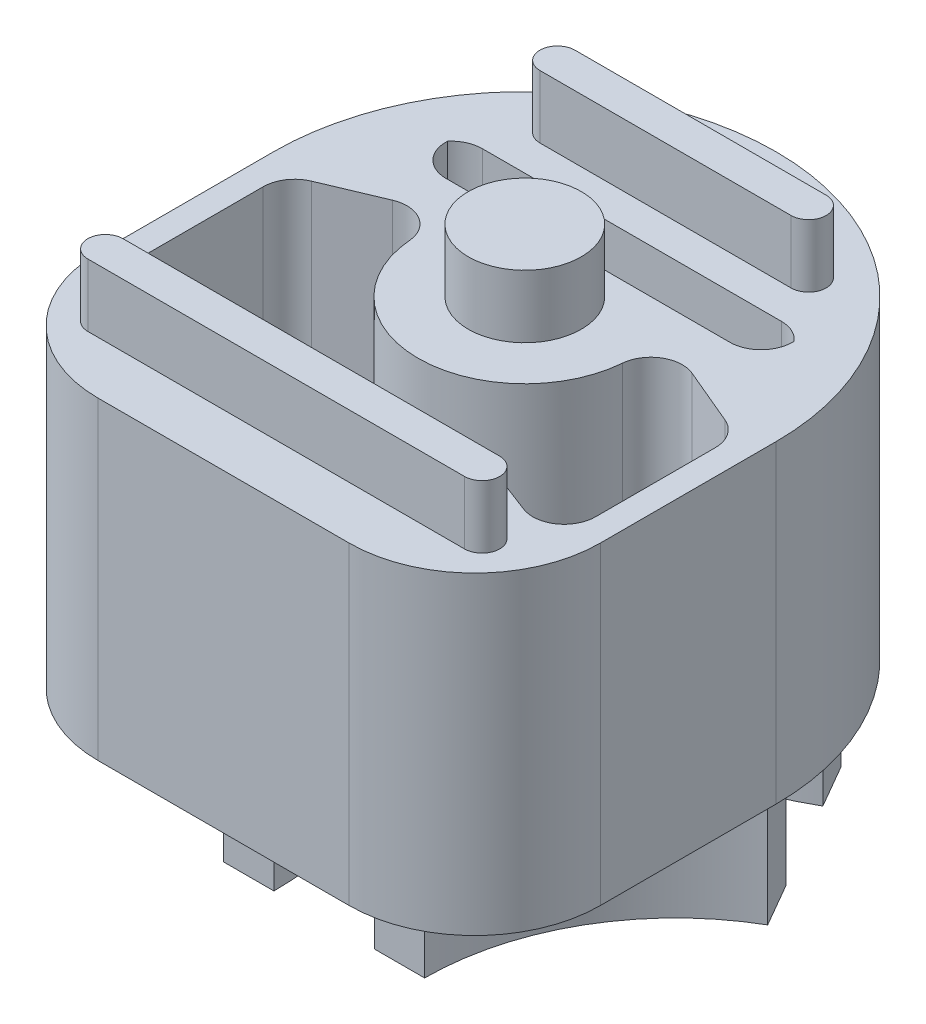
SolidWorks part; units mm, degrees
ref_plane "Front Plane" through (0, 0, 0) normal (0, 0, 1) x (1, 0, 0)
ref_plane "Top Plane" through (0, 0, 0) normal (0, 1, 0) x (1, 0, 0)
ref_plane "Right Plane" through (0, 0, 0) normal (1, 0, 0) x (0, 0, -1)
sketch "Sketch1" plane through (0, 0, 0) normal (0, 1, 0) x (1, 0, 0)
  circle A0 centre (0, 0) radius 28
  circle A1 centre (-28, -48.4974) radius 28
  circle A2 centre (28, -48.4974) radius 28
  arc A3 (-4.6726, -29.6339) -> (4.6726, -29.6339) centre (0, 0) ccw
  arc A4 (0, -37.7271) -> (-4.6726, -29.6339) centre (-28, -48.4974) ccw
  arc A5 (4.6726, -29.6339) -> (0, -37.7271) centre (28, -48.4974) ccw
  circle A6 centre (0, 0) radius 30 construction
  circle A7 centre (-28, -48.4974) radius 30 construction
  circle A8 centre (28, -48.4974) radius 30 construction
  circle A9 centre (0, 0) radius 24
  circle A10 centre (-28, -48.4974) radius 24
  circle A11 centre (28, -48.4974) radius 24
  circle A12 centre (0, 0) radius 20
  circle A13 centre (-28, -48.4974) radius 20
  circle A14 centre (28, -48.4974) radius 20
  dimension "D1" = 56
  dimension "D2" = 2
  dimension "D3" = 4
  dimension "D4" = 4
extrude "Boss-Extrude1" add sketch "Sketch1" along normal blind 10 contours A10 A13 | A9 A12 | A11 A14 | A5 A3 A4 region at (0, 0, 32.3316) region at (-23.3212, 0, 0) region at (-51.3212, 0, 48.4974) region at (4.6788, 0, 48.4974)
sketch "Sketch2" plane through (0, 10, 0) normal (0, 1, 0) x (1, 0, 0)
  line L0 (-20, -32.517) -> (-20, -56.5059)
  line L1 (-20, -56.5059) -> (20, -56.5059)
  line L2 (20, -56.5059) -> (20, -32.517)
  arc A0 (20, -32.517) -> (-20, -32.517) centre (0, -32.517) ccw
  dimension "D1" = 40
extrude "Boss-Extrude2" add sketch "Sketch2" along normal blind 25
sketch "Sketch3" plane through (0, 0, 0) normal (0, -1, 0) x (1, 0, 0)
  line L0 (0, 0) -> (28, 48.4974)
  line L1 (28, 48.4974) -> (-28, 48.4974)
  line L2 (-28, 48.4974) -> (0, 0)
  line L4 (-59.3942, 74.2986) -> (61.8263, 74.2986)
  line L5 (-59.3942, 74.2986) -> (-59.3942, -27.4652)
  line L6 (-59.3942, -27.4652) -> (61.8263, -27.4652)
  line L7 (61.8263, 74.2986) -> (61.8263, -27.4652)
  circle A0 centre (-28, 48.4974) radius 20 construction
  circle A1 centre (28, 48.4974) radius 20 construction
extrude "Cut-Extrude1" cut sketch "Sketch3" against normal blind 10
sketch "Sketch4" plane through (0, 35, 0) normal (0, 1, 0) x (1, 0, 0)
  line L0 (-10, -19.917) -> (10, -19.917) construction
  line L1 (-10, -18.517) -> (10, -18.517)
  line L2 (-10, -21.317) -> (10, -21.317)
  line L3 (-15, -50.917) -> (15, -50.917) construction
  line L4 (-15, -49.517) -> (15, -49.517)
  line L5 (-15, -52.317) -> (15, -52.317)
  circle A0 centre (0, -32.517) radius 4.5
  arc A1 (-10, -18.517) -> (-10, -21.317) centre (-10, -19.917) ccw
  arc A2 (10, -21.317) -> (10, -18.517) centre (10, -19.917) ccw
  arc A3 (-15, -49.517) -> (-15, -52.317) centre (-15, -50.917) ccw
  arc A4 (15, -52.317) -> (15, -49.517) centre (15, -50.917) ccw
  circle A5 centre (0, -32.517) radius 20 construction
  point P4 (0, -19.917)
  point P9 (0, -50.917)
  dimension "D1" = 9
  dimension "D2" = 12.6
  dimension "D3" = 2.8
  dimension "D4" = 20
  dimension "D5" = 2.8
  dimension "D6" = 30
  dimension "D7" = 18.4
extrude "Boss-Extrude4" add sketch "Sketch4" along normal blind 5
fillet "Fillet1" radius 10 2 edges at (-20, 22.5, 56.5059) (20, 22.5, 56.5059)
sketch "Sketch5" plane through (0, 35, 0) normal (0, 1, 0) x (1, 0, 0)
  line L0 (-18, -33.6914) -> (-7.9252, -29.4443)
  line L1 (7.9252, -29.4443) -> (18, -33.6914)
  line L2 (18, -33.6914) -> (18, -48.517)
  line L3 (18, -48.517) -> (10, -45.4515)
  line L4 (10, -45.4515) -> (-10, -45.4515)
  line L5 (-10, -45.4515) -> (-18, -48.517)
  line L6 (-18, -48.517) -> (-18, -33.6914)
  line L7 (-13.596, -24) -> (13.596, -24)
  line L8 (13.596, -24) -> (15, -27.5)
  line L9 (15, -27.5) -> (-15, -27.5)
  line L10 (-15, -27.5) -> (-13.596, -24)
  line L11 (-20, -32.517) -> (-20, -46.5059) construction
  line L12 (15, -49.517) -> (-15, -49.517) construction
  arc A0 (-7.9252, -29.4443) -> (7.9252, -29.4443) centre (0, -32.517) ccw
  arc A1 (-12, -20.7846) -> (12, -20.7846) centre (0, 0) ccw construction
  point P16 (-9.8615, -45.3649)
  point P17 (10, -45.4816)
  dimension "D5" = 8.5
  dimension "D1" = 15
  dimension "D2" = 15
  dimension "D3" = 3.5
  dimension "D4" = 2
  dimension "D6" = 20
  dimension "D7" = 1
extrude "Cut-Extrude2" cut sketch "Sketch5" against normal up to surface (25 mm away) up to face at (-10.2237, 10, 38.2343)
fillet "Fillet2" radius 2.5 4 edges at (15, 22.5, 27.5) (-15, 22.5, 27.5) (13.596, 22.5, 24) (-13.596, 22.5, 24)
fillet "Fillet3" radius 2.5 8 edges at (18, 22.5, 48.517) (10, 22.5, 45.4515) (-10, 22.5, 45.4515) (-18, 22.5, 48.517) (18, 22.5, 33.6914) (7.9252, 22.5, 29.4443) (-7.9252, 22.5, 29.4443) (-18, 22.5, 33.6914)
